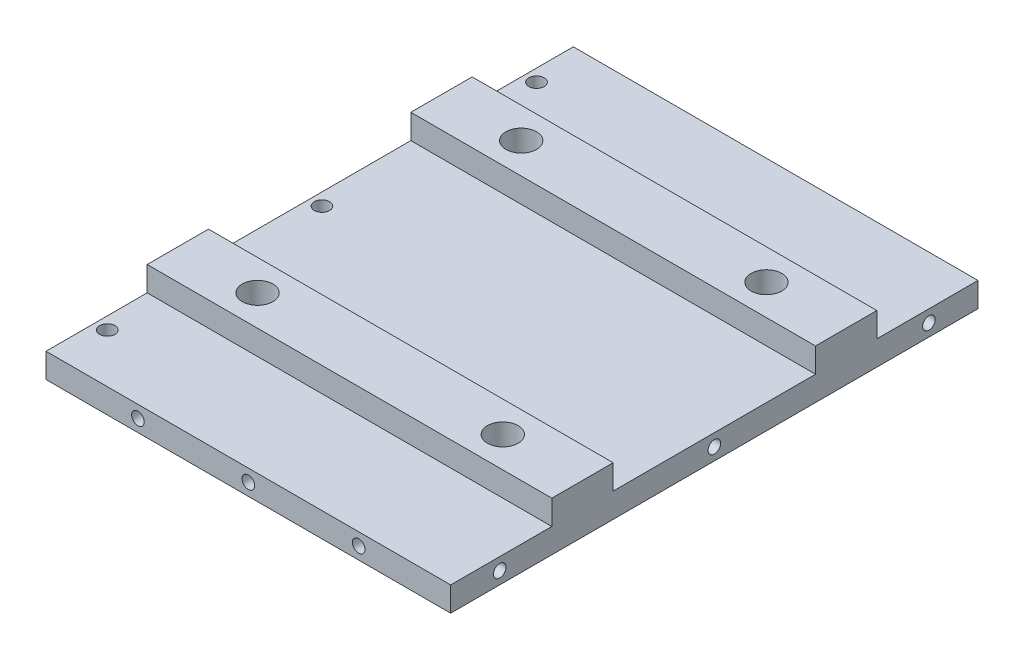
SolidWorks part; units mm, degrees
ref_plane "前视基准面" through (0, 0, 0) normal (0, 0, 1) x (1, 0, 0)
ref_plane "上视基准面" through (0, 0, 0) normal (0, 1, 0) x (1, 0, 0)
ref_plane "右视基准面" through (0, 0, 0) normal (1, 0, 0) x (0, 0, -1)
sketch "草图1" plane through (0, 0, 0) normal (0, 1, 0) x (1, 0, 0)
  line L0 (0, 0) -> (0, 43)
  line L1 (0, 0) -> (0, -43)
  line L2 (66, 43) -> (66, -43)
  line L3 (0, 43) -> (66, 43)
  line L4 (66, -43) -> (0, -43)
  circle A0 centre (2, 0) radius 1.25
  circle A1 centre (2, 35) radius 1.25
  circle A2 centre (2, -35) radius 1.25
  dimension "D1" = 2
  dimension "D2" = 2
extrude "凸台-拉伸1" add sketch "草图1" along normal blind 4
ref_plane "基准面1" through (0, 0, 43) normal (0, 0, 1) x (1, 0, 0)
sketch "草图2" plane through (0, 0, 43) normal (0, 0, 1) x (1, 0, 0)
  line L0 (0, 2) -> (15, 2)
  line L1 (66, 2) -> (51, 2)
  line L3 (33, 0) -> (33, 2)
hole_wizard "M2.5 螺纹孔1" positions "草图5" profile "草图6" tap size "M2.5" standard "GB"
sketch "草图5" plane through (0, 0, 43) normal (0, 0, 1) x (1, 0, 0)
  line L0 (66, 2) -> (51, 2) construction
  point P0 (15, 2)
  point P3 (33, 2)
  point P6 (51, 2)
sketch "草图6" plane through (15, 2, 43) normal (1, 0, 0) x (0, -1, 0)
  line L0 (0, 0) -> (0, 8.8659)
  line L1 (0, 8.8659) -> (1.025, 8.25)
  line L2 (1.025, 8.25) -> (1.025, 0)
  line L5 (1.025, 0) -> (0, 0)
  line L10 (0, 8.8659) -> (-1.025, 8.25) construction
  line L11 (0, -6.35) -> (0, 107.95) construction
  dimension "螺纹孔钻头直径" = 2.05
  dimension "螺纹孔钻头深度" = 8.25
  dimension "导头角度" = 118
cosmetic thread "孔螺蚊线1" parameters "D1"=6, "D2"=2.5
cosmetic thread "孔螺蚊线2" parameters "D1"=6, "D2"=2.5
cosmetic thread "孔螺蚊线3" parameters "D1"=6, "D2"=2.5
mirror "镜向1" about plane through (0, 0, 0) normal (0, 0, 1) of "M2.5 螺纹孔1"
ref_plane "基准面2" through (0, 4, 0) normal (0, 1, 0) x (1, 0, 0)
sketch "草图7" plane through (0, 4, 0) normal (0, 1, 0) x (1, 0, 0)
  line L0 (0, 0) -> (66, 0) construction
  line L2 (66, 16.5) -> (66, 26.5)
  line L3 (66, 26.5) -> (0, 26.5)
  line L4 (0, 26.5) -> (0, 16.5)
  line L5 (66, 16.5) -> (0, 16.5)
  line L6 (66, -16.5) -> (0, -16.5)
  line L7 (0, -26.5) -> (0, -16.5)
  line L8 (66, -26.5) -> (0, -26.5)
  line L9 (66, -16.5) -> (66, -26.5)
  circle A0 centre (13, 21.5) radius 2.5
  circle A2 centre (53, 21.5) radius 2.5
  circle A3 centre (53, -21.5) radius 2.5
  circle A5 centre (13, -21.5) radius 2.5
extrude "凸台-拉伸2" add sketch "草图7" along normal blind 4 contours A0 | A2 | A3 | A5 | L9 L6 L7 L8 A3 A5 | L5 L2 L3 L4 A2 A0 region at (33, 4, -21.5) region at (33, 4, 21.5) region at (13, 4, -21.5) region at (53, 4, -21.5) region at (53, 4, 21.5) region at (13, 4, 21.5)
extrude "切除-拉伸1" cut sketch "草图7<3>" against normal mid plane 8 contours A0 | A2 | A3 | A5
sketch "草图7<3>" plane through (0, 4, 0) normal (0, 1, 0) x (1, 0, 0) same geometry as "草图7"
ref_plane "基准面3" through (66, 0, 0) normal (1, 0, 0) x (0, 0, -1)
sketch "草图8" plane through (66, 0, 0) normal (1, 0, 0) x (0, 0, -1)
  circle A0 centre (0, 2) radius 1.25
  circle A1 centre (-35, 2) radius 1.25
  circle A2 centre (35, 2) radius 1.25
  dimension "D1" = 2
  dimension "D2" = 2
hole_wizard "M2.5 螺纹孔2" positions "草图9" profile "草图10" tap size "M2.5" standard "GB"
sketch "草图9" plane through (66, 0, 0) normal (1, 0, 0) x (0, 0, -1)
  point P0 (-35, 2)
  point P3 (0, 2)
  point P6 (35, 2)
sketch "草图10" plane through (66, 2, 35) normal (0, 1, 0) x (0, 0, -1)
  line L0 (0, 0) -> (0, 7.8659)
  line L1 (0, 7.8659) -> (1.025, 7.25)
  line L2 (1.025, 7.25) -> (1.025, 0)
  line L5 (1.025, 0) -> (0, 0)
  line L10 (0, 7.8659) -> (-1.025, 7.25) construction
  line L11 (0, -6.35) -> (0, 107.95) construction
  dimension "螺纹孔钻头直径" = 2.05
  dimension "螺纹孔钻头深度" = 7.25
  dimension "导头角度" = 118
cosmetic thread "孔螺蚊线4" parameters "D1"=5, "D2"=2.5
cosmetic thread "孔螺蚊线5" parameters "D1"=5, "D2"=2.5
cosmetic thread "孔螺蚊线6" parameters "D1"=5, "D2"=2.5
